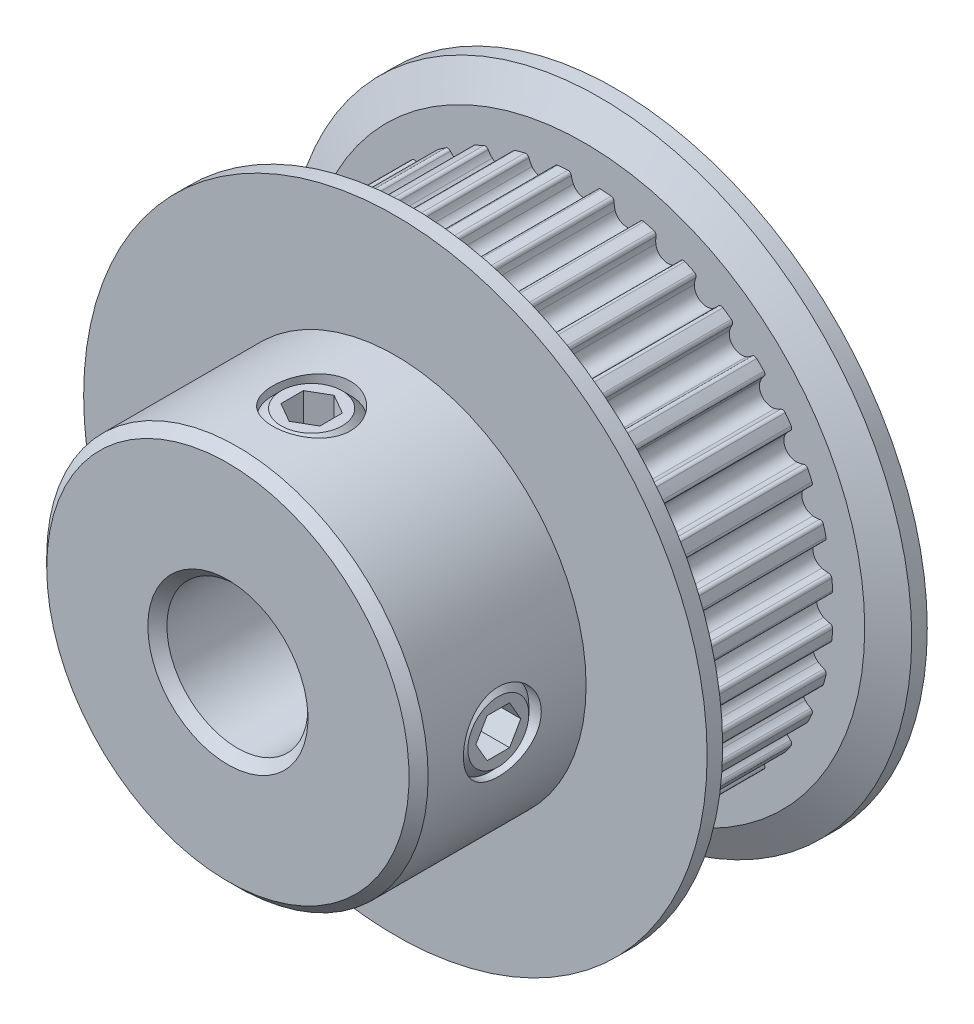
SolidWorks part; units mm, degrees
ref_plane "Front Plane" through (0, 0, 0) normal (0, 0, 1) x (1, 0, 0)
ref_plane "Top Plane" through (0, 0, 0) normal (0, 1, 0) x (1, 0, 0)
ref_plane "Right Plane" through (0, 0, 0) normal (1, 0, 0) x (0, 0, -1)
sketch "Sketch1" plane through (0, 0, 0) normal (0, 0, 1) x (1, 0, 0)
  line L1 (-1.8459, 10.4515) -> (1.8459, 10.4515) construction
  line L4 (0, 0) -> (0, 10.4515) construction
  line L5 (0, 10.4515) -> (0, 14.6064) construction
  line L6 (0, 11.4555) -> (1.9924, 11.2809) construction
  line L7 (1.9924, 11.2809) -> (2.8218, 11.1344) construction
  line L8 (1.9924, 11.2809) -> (1.8459, 10.4515) construction
  line L9 (-1.9924, 11.2809) -> (-1.8459, 10.4515) construction
  line L10 (-1.9482, 11.0308) -> (-2.4785, 14.0335)
  line L11 (-2.4785, 14.0335) -> (2.4785, 14.0335)
  line L12 (2.4785, 14.0335) -> (1.9482, 11.0308)
  circle A0 centre (0, 0) radius 11.4555 construction
  circle A1 centre (0, 0) radius 14.0335 construction
  circle A2 centre (0, 0) radius 11.2015 construction
  arc A3 (-0.4989, 10.7633) -> (0.4989, 10.7633) centre (0, 11.0065) ccw
  arc A4 (-0.4989, 10.7633) -> (-0.5884, 11.0497) centre (0.4, 11.2015) cw
  arc A5 (-1.9482, 11.0308) -> (-0.7467, 11.1766) centre (0, 0) cw
  arc A6 (-0.5884, 11.0497) -> (-0.7467, 11.1766) centre (-0.7367, 11.0269) ccw
  arc A7 (1.9482, 11.0308) -> (0.7467, 11.1766) centre (0, 0) ccw
  arc A8 (0.5884, 11.0497) -> (0.7467, 11.1766) centre (0.7367, 11.0269) cw
  arc A9 (0.4989, 10.7633) -> (0.5884, 11.0497) centre (-0.4, 11.2015) ccw
  point P6 (0, 20.9083)
  point P11 (0, 11.4555)
  point P13 (0, 14.0335)
  point P14 (0, 11.2015)
  dimension "D1" = 6.3019
  dimension "D2" = 3.1509
sketch "Sketch2" plane through (0, 0, 0) normal (1, 0, 0) x (0, 0, -1)
  line L0 (-8.7249, 3.175) -> (8.7249, 3.175)
  line L1 (-8.7249, 3.175) -> (-8.7249, 8.585)
  line L2 (-8.7249, 8.585) -> (-1.1851, 8.585)
  line L3 (-1.1851, 8.585) -> (-1.1851, 14.0335)
  line L4 (-1.1851, 14.0335) -> (0.2149, 14.0335) construction
  line L5 (0.2149, 14.0335) -> (0.2149, 11.2015) construction
  line L6 (0.2149, 11.2015) -> (7.3249, 11.2015)
  line L7 (7.3249, 11.2015) -> (7.3249, 14.0335) construction
  line L8 (7.3249, 14.0335) -> (8.7249, 14.0335) construction
  line L9 (8.7249, 14.0335) -> (8.7249, 3.175)
  line L10 (-8.7249, 0) -> (8.7249, 0) construction
  line L11 (8.0249, 14.0335) -> (7.3249, 12.6175)
  line L12 (0.2149, 12.6175) -> (-0.4851, 14.0335)
  line L13 (-1.1851, 14.0335) -> (-0.4851, 14.0335)
  line L14 (0.2149, 12.6175) -> (0.2149, 11.2015)
  line L15 (7.3249, 11.2015) -> (7.3249, 12.6175)
  line L16 (8.0249, 14.0335) -> (8.7249, 14.0335)
  arc A0 (0.2149, 12.6175) -> (-0.4851, 14.0335) centre (-1.5673, 12.6175) ccw construction
  arc A1 (7.3249, 12.6175) -> (8.0249, 14.0335) centre (9.1071, 12.6175) cw construction
  point P12 (0.2149, 12.6175)
  point P14 (-0.4851, 14.0335)
  point P20 (7.3249, 12.6175)
  point P21 (8.0249, 14.0335)
  point P25 (7.3249, 0)
  point P26 (0.2149, 0)
revolve "Revolve1" add sketch "Sketch2" angle 360 mid plane about L10
sketch "Sketch3" plane through (0, 0, 0) normal (0, 0, 1) x (1, 0, 0)
  line L6 (2.4785, 14.0335) -> (-2.4785, 14.0335)
  line L7 (1.9482, 11.0308) -> (2.4785, 14.0335)
  line L8 (-2.4785, 14.0335) -> (-1.9482, 11.0308)
  line L9 (2.4785, 14.0335) -> (-2.4785, 14.0335)
  line L10 (1.9482, 11.0308) -> (2.4785, 14.0335)
  line L11 (-2.4785, 14.0335) -> (-1.9482, 11.0308)
  arc A8 (1.9482, 11.0308) -> (0.7467, 11.1766) centre (0, 0) ccw
  arc A9 (0.7467, 11.1766) -> (0.5884, 11.0497) centre (0.7367, 11.0269) ccw
  arc A10 (0.4989, 10.7633) -> (0.5884, 11.0497) centre (-0.4, 11.2015) ccw
  arc A11 (-0.4989, 10.7633) -> (0.4989, 10.7633) centre (0, 11.0065) ccw
  arc A12 (-0.5884, 11.0497) -> (-0.4989, 10.7633) centre (0.4, 11.2015) ccw
  arc A13 (-0.5884, 11.0497) -> (-0.7467, 11.1766) centre (-0.7367, 11.0269) ccw
  arc A14 (-0.7467, 11.1766) -> (-1.9482, 11.0308) centre (0, 0) ccw
  arc A15 (1.9482, 11.0308) -> (0.7467, 11.1766) centre (0, 0) ccw
  arc A16 (0.7467, 11.1766) -> (0.5884, 11.0497) centre (0.7367, 11.0269) ccw
  arc A17 (0.4989, 10.7633) -> (0.5884, 11.0497) centre (-0.4, 11.2015) ccw
  arc A18 (-0.4989, 10.7633) -> (0.4989, 10.7633) centre (0, 11.0065) ccw
  arc A19 (-0.5884, 11.0497) -> (-0.4989, 10.7633) centre (0.4, 11.2015) ccw
  arc A20 (-0.5884, 11.0497) -> (-0.7467, 11.1766) centre (-0.7367, 11.0269) ccw
  arc A21 (-0.7467, 11.1766) -> (-1.9482, 11.0308) centre (0, 0) ccw
  dimension "D1" = 0
extrude "Cut-Extrude1" cut sketch "Sketch3" against normal up to vertex (7.3249 mm away) from vertex up to point (0, 11.2015, -7.3249) starting at point (0, 11.2015, -0.2149)
pattern_circular "CirPattern1" count 36 over 360 about axis through (0, 0, 8.7249) along (0, 0, 1) of "Cut-Extrude1"
sketch "Sketch4" plane through (0, 0, 0) normal (1, 0, 0) x (0, -1, 0)
  line L0 (0, -1.1851) -> (0, -8.7249) construction
  line L1 (-8.585, -1.1851) -> (8.585, -1.1851) construction
  line L2 (-8.585, -8.7249) -> (8.585, -8.7249) construction
  circle A0 centre (0, -4.955) radius 1.7526
extrude "Cut-Extrude2" cut sketch "Sketch4" along normal through all
ref_plane "Plane1" through (0, 0, 4.955) normal (0, 0, 1) x (1, 0, 0)
sketch "Sketch5" plane through (0, 0, 4.955) normal (0, 0, 1) x (1, 0, 0)
  line L0 (0, 0.1664) -> (0, 8.585) construction
  line L1 (3.175, -1.3716) -> (3.175, 0)
  line L2 (3.556, -1.7526) -> (8.0232, -1.7526)
  line L3 (3.175, 0) -> (8.585, 0) construction
  line L4 (3.175, 0) -> (8.4042, 0)
  line L5 (8.4042, 0) -> (8.4042, -1.3716)
  line L6 (3.556, -1.7526) -> (3.175, -1.3716)
  line L7 (8.4042, -1.3716) -> (8.0232, -1.7526)
  circle A0 centre (0, 0) radius 8.585 construction
  circle A1 centre (0, 0) radius 3.175 construction
  point P2 (3.175, -1.7526)
  point P11 (8.4042, -1.7526)
revolve "Revolve2" add sketch "Sketch5" angle 360 mid plane about L4
sketch "Sketch6" plane through (8.4042, 5.3841, 0) normal (-1, 0, 0) x (0, -1, 0)
  line L1 (5.3841, 5.9669) -> (4.5078, 5.4609)
  line L2 (4.5078, 5.4609) -> (4.5078, 4.4491)
  line L3 (4.5078, 4.4491) -> (5.3841, 3.9431)
  line L4 (5.3841, 3.9431) -> (6.2604, 4.4491)
  line L5 (6.2604, 4.4491) -> (6.2604, 5.4609)
  line L6 (6.2604, 5.4609) -> (5.3841, 5.9669)
  circle A0 centre (5.3841, 4.955) radius 0.8763 construction
  dimension "D1" = 1.7526
extrude "Cut-Extrude3" cut sketch "Sketch6" along normal blind 1.3144
pattern_circular "CirPattern2" count 2 over 90 about axis through (0, 0, 8.7249) along (0, 0, 1) of "Cut-Extrude2", "Revolve2", "Cut-Extrude3"
chamfer "Chamfer1" distance 0.4293 angle 45 2 edges at (3.175, 0, 8.7249) (8.585, 0, 8.7249)
ref_axis "Center Axis 1" through (0, 0, -8.7249) along (0, 0, 1)
ref_plane "Contact Plane 1" through (0, 0, 8.7249) normal (0, 0, 1) x (1, 0, 0)
ref_plane "Contact Plane 2" through (0, 0, -8.7249) normal (0, 0, -1) x (-1, 0, 0)
equation "\"D2@Sketch1\" = \"D1@Sketch1\"/2"
equation "\"D1@Sketch6\" = \"Set Screw@Sketch4\" / 2"
equation "\"D1@Cut-Extrude3\" = \"D1@Sketch6\"*.75"
equation "\"D1@Chamfer1\"=\"Hub Dia@Sketch2\"*.025"
